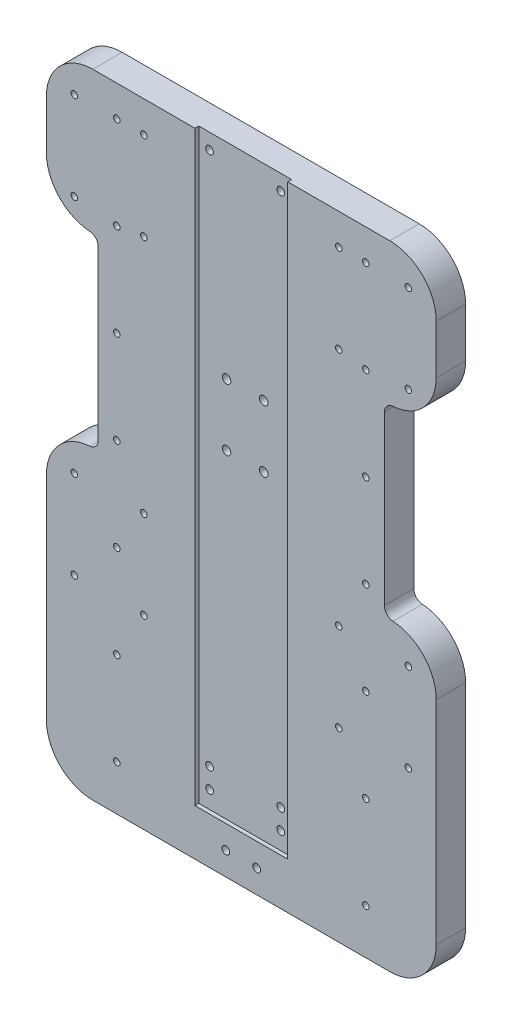
SolidWorks part; units mm, degrees
ref_plane "Piano frontale" through (0, 0, 0) normal (0, 0, 1) x (1, 0, 0)
ref_plane "Piano superiore" through (0, 0, 0) normal (0, 1, 0) x (1, 0, 0)
ref_plane "Piano destro" through (0, 0, 0) normal (1, 0, 0) x (0, 0, -1)
sketch "Schizzo1" plane through (0, 0, 0) normal (0, 0, 1) x (1, 0, 0)
  line L1 (126, -250) -> (-126, -250)
  line L2 (126, -250) -> (126, 250)
  line L3 (126, 250) -> (-126, 250)
  line L4 (-126, -250) -> (-126, 250)
  line L5 (126, -250) -> (-126, 250) construction
  line L6 (126, 250) -> (-126, -250) construction
  point P0 (0, 0)
  dimension "D1" = 252
  dimension "D2" = 500
extrude "Estrusione-Estrusione1" add sketch "Schizzo1" along normal blind 19
sketch "Schizzo2" plane through (0, 0, 19) normal (0, 0, 1) x (1, 0, 0)
  line L0 (1265.2426, 21.4119) -> (-695.7574, 21.4119) construction
  line L1 (1265.2426, 13.5541) -> (-695.7574, 13.5541) construction
  line L2 (1265.2426, 53.5541) -> (-695.7574, 53.5541) construction
  line L3 (1265.2426, 61.4119) -> (-695.7574, 61.4119) construction
  line L4 (-126, 250) -> (-126, -250)
  line L5 (-126, -250) -> (126, -250)
  line L6 (126, -250) -> (126, 250)
  line L7 (126, 250) -> (-126, 250)
  line L8 (-126, 250) -> (-126, -250) construction
  line L9 (-126, -250) -> (126, -250) construction
  line L10 (126, -250) -> (126, 250) construction
  line L11 (126, 250) -> (-126, 250) construction
  line L12 (1265.2426, 21.4119) -> (-695.7574, 21.4119) construction
  line L13 (1265.2426, 13.5541) -> (-695.7574, 13.5541) construction
  line L14 (1265.2426, 53.5541) -> (-695.7574, 53.5541) construction
  line L15 (1265.2426, 61.4119) -> (-695.7574, 61.4119) construction
  line L16 (126, -45.017) -> (-126, -45.017) construction
  line L17 (126, -25.017) -> (-126, -25.017) construction
  line L18 (126, -45.017) -> (-126, -45.017) construction
  line L19 (126, -25.017) -> (-126, -25.017) construction
  line L20 (-126, -45.017) -> (-126, -25.017) construction
  line L21 (126, -35.017) -> (-126, -35.017) construction
  line L22 (-126, -45.017) -> (126, -45.017) construction
  line L23 (-126, -45.017) -> (-126, -25.017) construction
  line L24 (-126, -25.017) -> (126, -25.017) construction
  line L25 (126, -45.017) -> (126, -25.017) construction
  circle A0 centre (110, 17.483) radius 3.9289
  circle A1 centre (110, 57.483) radius 3.9289
  circle A2 centre (-110, 17.483) radius 3.9289
  circle A3 centre (-110, 57.483) radius 3.9289
  circle A4 centre (110, -35.017) radius 3.5
  circle A5 centre (-110, -35.017) radius 3.5
  circle A6 centre (55, -35.017) radius 3.5
  circle A8 centre (-55, -35.017) radius 3.5
  circle A9 centre (20, -35.017) radius 3.5
  circle A10 centre (-20, -35.017) radius 3.5
  circle A11 centre (165, -35.017) radius 3.5 [skipped]
  dimension "D2" = 16
  dimension "D3" = 7.8579
  dimension "D4" = 16
  dimension "D5" = 7.8579
  dimension "D6" = 7
  dimension "D7" = 7
  dimension "D8" = 2
  dimension "D1" = 0
  dimension "D9" = 2
  dimension "D10" = 2
  dimension "D11" = 2
sketch "Schizzo3" plane through (0, 250, 0) normal (0, 1, 0) x (1, 0, 0)
  line L0 (126, -19) -> (-126, -19) construction
  line L1 (30, -16.5) -> (-30, -16.5)
  line L2 (30, -16.5) -> (30, -19)
  line L3 (30, -19) -> (-30, -19)
  line L4 (-30, -16.5) -> (-30, -19)
  line L5 (126, -19) -> (126, 0) construction
  line L6 (-126, -19) -> (-126, 0) construction
  line L7 (126, -19) -> (-126, -19) construction
  dimension "D1" = 2.5
  dimension "D2" = 96
  dimension "D3" = 96
extrude "Taglio-Estrusione1" cut sketch "Schizzo3" against normal through all
sketch "Schizzo4" plane through (0, 0, 16.5) normal (0, 0, 1) x (1, 0, 0)
  line L0 (30, -250) -> (30, 250) construction
  line L2 (30, 250) -> (-30, 250) construction
  line L3 (30, -250) -> (30, 250) construction
  line L6 (-30, 250) -> (-126, 250) construction
  line L7 (-30, -250) -> (-30, 250) construction
  point P11 (23, -118)
  point P14 (-23, -118)
  point P15 (-23, -105)
  point P16 (23, -105)
  point P17 (23, 240)
  point P18 (-23, 240)
  dimension "D1" = 46
  dimension "D2" = 13
  dimension "D3" = 13
  dimension "D4" = 46
  dimension "D5" = 7
  dimension "D6" = 345
  dimension "D7" = 10
  dimension "D8" = 46
  dimension "D9" = 7
  dimension "D10" = 10
  dimension "D11" = 7
  dimension "D12" = 7
sketch "Schizzo5" plane through (0, 0, 19) normal (0, 0, 1) x (1, 0, 0)
  point P4 (80.5006, 170)
  point P7 (80.5006, 110)
  point P16 (80.5006, 50)
  point P17 (80.5006, -10)
  point P18 (80.5006, -70)
  point P19 (80.5006, -130)
  point P20 (80.5006, 230)
hole_wizard "Tap Drill for M5 Tap2" positions "Sketch7" profile "Sketch8" hole size "M5" standard "ISO"
sketch "Sketch7" plane through (0, 0, 19) normal (0, 0, 1) x (1, 0, 0)
  point P0 (80.5006, -130)
  point P3 (80.5006, -70)
  point P7 (80.5006, -10)
  point P10 (80.5006, 50)
  point P13 (80.5006, 110)
  point P16 (80.5006, 170)
  point P19 (80.5006, 230)
sketch "Sketch8" plane through (80.5006, -130, 19) normal (1, 0, 0) x (0, -1, 0)
  line L0 (0, 0) -> (0, 37.8618)
  line L1 (0, 37.8618) -> (2.1, 36.6)
  line L2 (2.1, 36.6) -> (2.1, 0)
  line L5 (2.1, 0) -> (0, 0)
  line L10 (0, 37.8618) -> (-2.1, 36.6) construction
  line L11 (0, -6.35) -> (0, 107.95) construction
  dimension "Hole Dia." = 4.2
  dimension "Hole Depth" = 36.6
  dimension "Drill Angle" = 118
sketch "Schizzo6" plane through (0, 0, 19) normal (0, 0, 1) x (1, 0, 0)
  line L0 (126, -250) -> (126, 250) construction
  line L2 (126, 250) -> (30, 250) construction
  point P23 (108, 172.8083)
  point P26 (63, 172.8083)
  point P27 (63, 229.8083)
  point P28 (108, 229.8083)
  dimension "D1" = 45
  dimension "D2" = 45
  dimension "D3" = 57
  dimension "D4" = 57
  dimension "D5" = 18
  dimension "D6" = 20.1917
  dimension "D7" = 20.1917
  dimension "D8" = 18
hole_wizard "Tap Drill for M5 Tap1" positions "Sketch14" profile "Sketch15" hole size "M5" standard "ISO"
sketch "Sketch14" plane through (0, 0, 19) normal (0, 0, 1) x (1, 0, 0)
  point P0 (108, 172.8083)
  point P3 (108, 229.8083)
  point P6 (63, 229.8083)
  point P9 (63, 172.8083)
  point P12 (63, 17.8083)
  point P14 (63, -39.1917)
  point P16 (108, -39.1917)
  point P18 (108, 17.8083)
sketch "Sketch15" plane through (108, 172.8083, 19) normal (1, 0, 0) x (0, -1, 0)
  line L0 (0, 0) -> (0, 37.8618)
  line L1 (0, 37.8618) -> (2.1, 36.6)
  line L2 (2.1, 36.6) -> (2.1, 0)
  line L5 (2.1, 0) -> (0, 0)
  line L10 (0, 37.8618) -> (-2.1, 36.6) construction
  line L11 (0, -6.35) -> (0, 107.95) construction
  dimension "Hole Dia." = 4.2
  dimension "Hole Depth" = 36.6
  dimension "Drill Angle" = 118
hole_wizard "Tap Drill for M6 Tap4" positions "Sketch9" profile "Sketch10" hole size "M6" standard "ISO"
sketch "Sketch9" plane through (0, 0, 16.5) normal (0, 0, 1) x (1, 0, 0)
  point P0 (23, -118)
  point P3 (23, -105)
  point P6 (-23, -118)
  point P9 (-23, -105)
  point P12 (23, 240)
  point P15 (-23, 240)
sketch "Sketch10" plane through (23, -118, 16.5) normal (1, 0, 0) x (0, -1, 0)
  line L0 (0, 0) -> (0, 38.1022)
  line L1 (0, 38.1022) -> (2.5, 36.6)
  line L2 (2.5, 36.6) -> (2.5, 0)
  line L5 (2.5, 0) -> (0, 0)
  line L10 (0, 38.1022) -> (-2.5, 36.6) construction
  line L11 (0, -6.35) -> (0, 107.95) construction
  dimension "Hole Dia." = 5
  dimension "Hole Depth" = 36.6
  dimension "Drill Angle" = 118
sketch "Sketch11" plane through (0, 0, 16.5) normal (0, 0, 1) x (1, 0, 0)
  line L0 (0, -250) -> (0, 250) construction
  line L1 (30, -250) -> (-30, -250) construction
  line L2 (30, 250) -> (-30, 250) construction
ref_plane "Plane1" through (0, 0, 0) normal (-1, 0, 0) x (0, 0, 1)
mirror "Mirror1" about plane through (0, 0, 0) normal (-1, 0, 0) of "Tap Drill for M5 Tap2"
mirror "Mirror2" about plane through (0, 0, 0) normal (-1, 0, 0) of "Tap Drill for M5 Tap1"
sketch "Sketch16" plane through (0, 0, 0) normal (0, 0, -1) x (-1, 0, 0)
  line L0 (126, 250) -> (126, -250) construction
  line L1 (126, -317.9299) -> (-126, -317.9299)
  line L2 (126, -317.9299) -> (126, -159.25)
  line L3 (126, -159.25) -> (-126, -159.25)
  line L4 (-126, -317.9299) -> (-126, -159.25)
  line L5 (-126, -250) -> (-126, 250) construction
  line L9 (-12.9, -159.25) -> (25.2, -159.25) construction
extrude "Cut-Extrude1" cut sketch "Sketch16" against normal blind 28
sketch "Sketch26" plane through (0, 0, 16.5) normal (0, 0, 1) x (1, 0, 0)
  line L0 (30, -159.25) -> (30, 250) construction
  line L1 (-30, -159.25) -> (30, -159.25)
  line L2 (-30, -159.25) -> (-30, -129.25)
  line L3 (-30, -129.25) -> (30, -129.25)
  line L4 (30, -159.25) -> (30, -129.25)
  dimension "D1" = 30
extrude "Boss-Extrude1" add sketch "Sketch26" along normal up to surface (2.5 mm away) up to face at (-78, 45.375, 19)
hole_wizard "M5 Clearance Hole1" positions "Sketch17" profile "Sketch18" hole size "M5" standard "ISO" end condition through all
sketch "Sketch17" plane through (0, 0, 16.5) normal (0, 0, 1) x (1, 0, 0)
  line L0 (12, 77.3083) -> (-12, 117.3083) construction
  line L1 (-12, 117.3083) -> (-12, 77.3083) construction
  line L2 (-12, 77.3083) -> (12, 117.3083) construction
  line L3 (12, 117.3083) -> (12, 77.3083) construction
  line L4 (12, 77.3083) -> (-12, 77.3083) construction
  line L7 (-12, 117.3083) -> (12, 117.3083) construction
  point P0 (-12, 77.3083)
  point P2 (12, 77.3083)
  point P4 (12, 117.3083)
  point P6 (-12, 117.3083)
  dimension "D1" = 40
  dimension "D2" = 24
sketch "Sketch18" plane through (-12, 77.3083, 16.5) normal (1, 0, 0) x (0, -1, 0)
  line L0 (0, 0) -> (0, 16.5)
  line L1 (0, 16.5) -> (2.75, 16.5)
  line L2 (2.75, 16.5) -> (2.75, 0)
  line L5 (2.75, 0) -> (0, 0)
  line L11 (0, -6.35) -> (0, 107.95) construction
  dimension "Thru Hole Dia." = 5.5
  dimension "Thru Hole Depth" = 16.5
sketch "Sketch19" plane through (0, -195.45, 0) normal (0, -1, 0) x (-1, 0, 0)
  line L0 (0, -70.7) -> (0, 68.239) construction
  line L1 (126, -9.5) -> (-126, -9.5) construction
  line L2 (126, -19) -> (126, 0) construction
  line L3 (-126, -19) -> (-126, 0) construction
  line L5 (28.2, 0) -> (-28.2, 0) construction
  point P8 (20, -9.5)
  point P9 (-20, -9.5)
  point P12 (-20, 9.5)
  point P13 (20, 9.5)
  dimension "D1" = 20
hole_wizard "Tap Drill for M6 Tap2" positions "Sketch22" profile "Sketch23" hole size "M6" standard "ISO"
sketch "Sketch22" plane through (0, -159.25, 0) normal (0, -1, 0) x (-1, 0, 0)
  point P0 (20, -7.125)
  point P2 (-20, -7.125)
sketch "Sketch23" plane through (-20, -159.25, 7.125) normal (1, 0, 0) x (0, 0, -1)
  line L0 (0, 0) -> (0, 31.5022)
  line L1 (0, 31.5022) -> (2.5, 30)
  line L2 (2.5, 30) -> (2.5, 0)
  line L5 (2.5, 0) -> (0, 0)
  line L10 (0, 31.5022) -> (-2.5, 30) construction
  line L11 (0, -6.35) -> (0, 107.95) construction
  dimension "Hole Dia." = 5
  dimension "Hole Depth" = 30
  dimension "Drill Angle" = 118
hole_wizard "Tap Drill for M6 Tap3" positions "Sketch24" profile "Sketch25" hole size "M6" standard "ISO" end condition through all
sketch "Sketch24" plane through (0, 0, 0) normal (0, 0, -1) x (-1, 0, 0)
  point P0 (-10, -144.25)
  point P6 (10, -144.25)
sketch "Sketch25" plane through (10, -144.25, 0) normal (1, 0, 0) x (0, 1, 0)
  line L0 (0, 0) -> (0, 19)
  line L1 (0, 19) -> (2.5, 19)
  line L2 (2.5, 19) -> (2.5, 0)
  line L5 (2.5, 0) -> (0, 0)
  line L11 (0, -6.35) -> (0, 107.95) construction
  dimension "Thru Hole Dia." = 5
  dimension "Thru Hole Depth" = 19
sketch "Sketch27" plane through (0, 0, 19) normal (0, 0, 1) x (1, 0, 0)
  line L2 (-126, 38.082) -> (-126, 158.222)
  line L4 (-92.5, 38.082) -> (-92.5, 158.222)
  line L5 (-126, 38.082) -> (-92.5, 38.082)
  line L7 (-126, 158.222) -> (-92.5, 158.222)
  line L9 (-92.5, 40.082) -> (-92.5, 156.222) construction
  line L10 (-126, 40.082) -> (-126, 156.222) construction
  line L11 (-128, 158.222) -> (-90.5, 158.222) construction
  line L12 (-128, 38.082) -> (-128, 158.222) construction
  line L13 (-128, 38.082) -> (-90.5, 38.082) construction
  line L14 (-126, 40.082) -> (-92.5, 40.082) construction
  line L15 (-90.5, 38.082) -> (-90.5, 158.222) construction
  line L16 (-126, 156.222) -> (-92.5, 156.222) construction
  line L17 (-126, 98.152) -> (126, 98.152) construction
  line L18 (126, -159.25) -> (126, 250) construction
  line L19 (126, 98.152) -> (0, 98.152) construction
  line L20 (0, 98.152) -> (0, 87.9155) construction
  line L21 (-126, 38.082) -> (-92.5, 38.082)
  line L22 (-126, 158.222) -> (-92.5, 158.222)
  line L23 (126, 158.222) -> (92.5, 158.222)
  line L24 (126, 38.082) -> (92.5, 38.082)
  line L25 (126, 158.222) -> (92.5, 158.222)
  line L26 (126, 38.082) -> (92.5, 38.082)
  line L27 (92.5, 38.082) -> (92.5, 158.222)
  line L28 (126, 38.082) -> (126, 158.222)
  line M11 (-126, 250) -> (-126, -159.25)
  line M13 (126, -159.25) -> (126, 250)
  dimension "D1" = 2
extrude "Cut-Extrude2" cut sketch "Sketch27" against normal blind 76.9911 contours L27 L24 L23 M13 | L7 L5 L4 M11 region at (-109.25, 98.152, 19) region at (109.25, 98.152, 19)
fillet "Fillet1" radius 30 4 edges at (126, 158.222, 9.5) (126, 38.082, 9.5) (-126, 158.222, 9.5) (-126, 38.082, 9.5)
fillet "Fillet2" radius 30 4 edges at (126, 250, 9.5) (-126, 250, 9.5) (-126, -159.25, 9.5) (126, -159.25, 9.5)
fillet "Fillet3" radius 6 4 edges at (92.5, 158.222, 9.5) (92.5, 38.082, 9.5) (-92.5, 38.082, 9.5) (-92.5, 158.222, 9.5)
equation "\"D3@Schizzo3\"=\"D2@Schizzo3\""
equation "\"D11@Schizzo4\"=\"D5@Schizzo4\""
